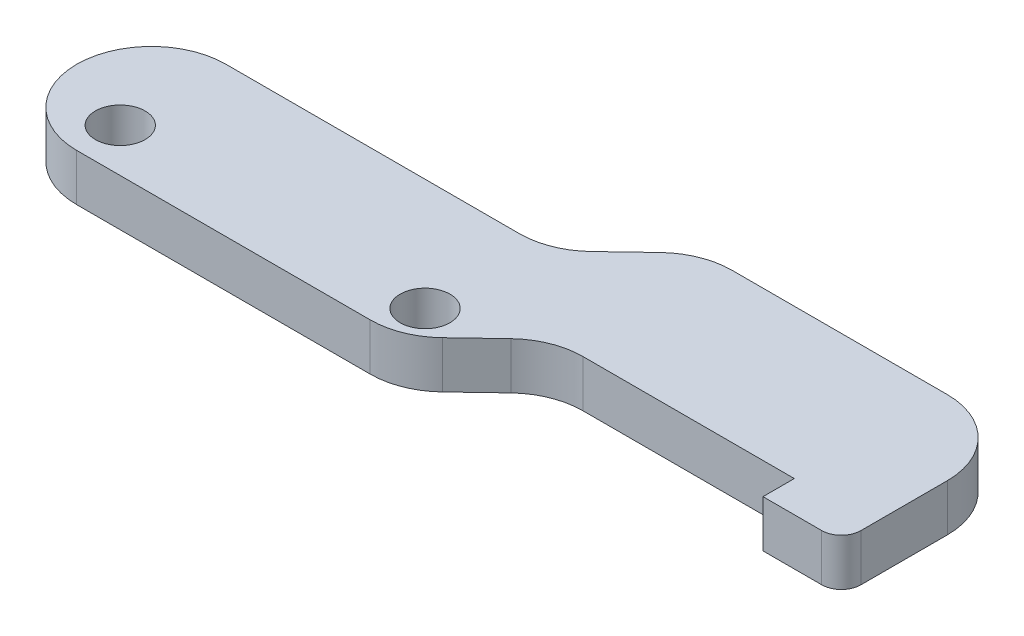
SolidWorks part; units mm, degrees
ref_plane "Front Plane" through (0, 0, 0) normal (0, 0, 1) x (1, 0, 0)
ref_plane "Top Plane" through (0, 0, 0) normal (0, 1, 0) x (1, 0, 0)
ref_plane "Right Plane" through (0, 0, 0) normal (1, 0, 0) x (0, 0, -1)
sketch "Sketch1" plane through (0, 0, 0) normal (0, 1, 0) x (1, 0, 0)
  line L2 (-317.5, -34.7266) -> (-317.5, 84.3359)
  line L4 (317.5, 24.8047) -> (317.5, 143.8672)
  line L5 (-317.5, 84.3359) -> (0, 84.3359)
  line L6 (-317.5, -34.7266) -> (0, -34.7266)
  line L7 (0, 84.3359) -> (62.5, 143.8672)
  line L8 (62.5, 143.8672) -> (317.5, 143.8672)
  line L9 (0, -55) -> (0, 55) construction
  line L10 (0, -34.7266) -> (62.5, 24.8047)
  line L12 (317.5, 24.8047) -> (317.5, -0.1953)
  line L13 (317.5, -0.1953) -> (255, -0.1953)
  line L14 (255, -0.1953) -> (255, 24.8047)
  line L15 (62.5, 24.8047) -> (255, 24.8047)
  line L16 (-55, 0) -> (55, 0) construction
  circle A0 centre (-257.9688, 0) radius 19.8438
  circle A1 centre (-9.8397, -4.9609) radius 19.8438
  point P0 (0, 0)
  dimension "Knuckle Diameter" = 39.6875
  dimension "Grasper Length" = 635
  dimension "Grasper Height" = 59.5312
  dimension "Grasper Length Div2" = 317.5
  dimension "Grasper End Length" = 255
  dimension "Grasper Width1" = 119.0625
  dimension "Gripper Length" = 62.5
  dimension "Gripper Width" = 25
  dimension "Knuckle Hole Spacing" = 59.5312
  dimension "Knuckle Hole Spacing1" = 4.9609
  dimension "Hole to Bottom Distance" = 34.7266
extrude "Boss-Extrude1" add sketch "Sketch1" along normal blind 37.5
fillet "Fillet1" radius 59.5312 7 edges at (62.5, 18.75, -24.8047) (0, 18.75, 34.7266) (0, 18.75, -84.3359) (62.5, 18.75, -143.8672) (317.5, 18.75, -143.8672) (-317.5, 18.75, 34.7266) (-317.5, 18.75, -84.3359)
fillet "Fillet3" radius 15.625 1 edges at (317.5, 18.75, 0.1953)
